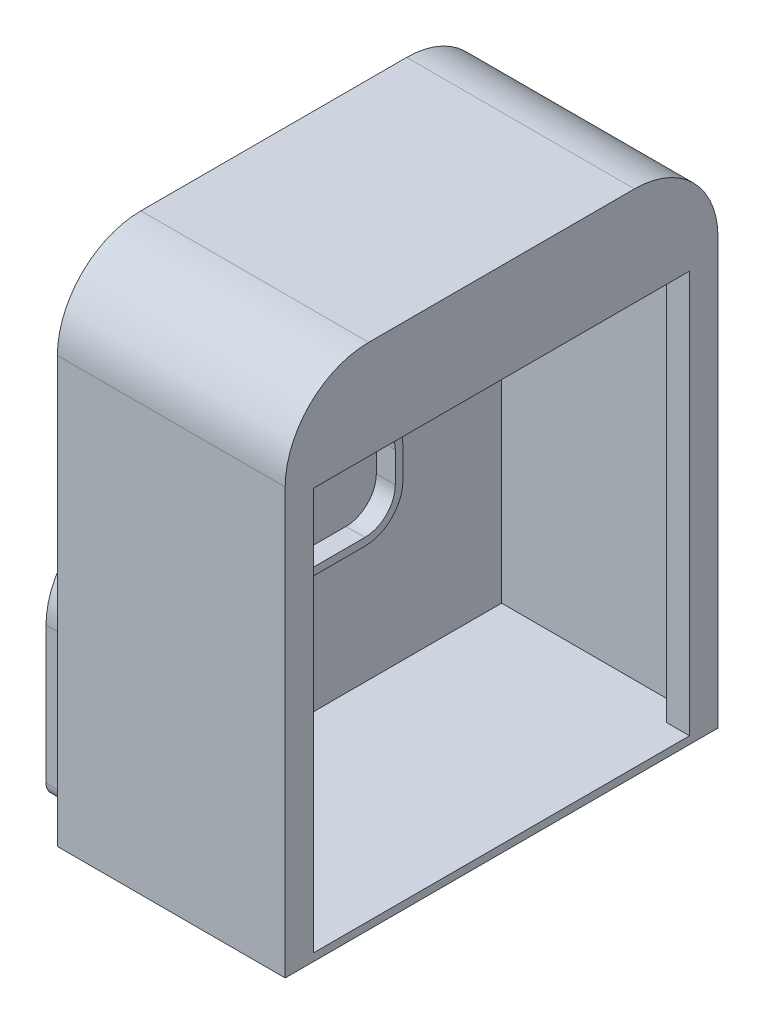
SolidWorks part; units mm, degrees
ref_plane "Front Plane" through (0, 0, 0) normal (0, 0, 1) x (1, 0, 0)
ref_plane "Top Plane" through (0, 0, 0) normal (0, 1, 0) x (1, 0, 0)
ref_plane "Right Plane" through (0, 0, 0) normal (1, 0, 0) x (0, 0, -1)
sketch "Sketch2" plane through (0, 0, 0) normal (1, 0, 0) x (0, 0, -1)
  line L1 (-7, -6) -> (7, -6)
  line L2 (-11, -2) -> (-11, 2)
  line L3 (-7, 6) -> (7, 6)
  line L4 (11, -2) -> (11, 2)
  line L5 (-11, -6) -> (11, 6) construction
  line L6 (-11, 6) -> (11, -6) construction
  arc A0 (-7, -6) -> (-11, -2) centre (-7, -2) cw
  arc A1 (7, 6) -> (11, 2) centre (7, 2) cw
  arc A2 (7, -6) -> (11, -2) centre (7, -2) ccw
  arc A3 (-11, 2) -> (-7, 6) centre (-7, 2) cw
  point P0 (0, 0)
  dimension "D3" = 4
  dimension "D1" = 22
  dimension "D2" = 12
extrude "Extrude-Thin1" add sketch "Sketch2" along normal blind 5 thin thin type one direction wall 1
sketch "Sketch3" plane through (0, 0, 0) normal (1, 0, 0) x (0, 0, -1)
  line L0 (27.5, -25) -> (-27.5, -25)
  line L1 (27.5, -25) -> (27.5, 30)
  line L2 (-27.5, -25) -> (-27.5, 30)
  line L3 (17.5, 40) -> (-17.5, 40)
  arc A0 (27.5, 30) -> (17.5, 40) centre (17.5, 30) ccw
  arc A1 (-27.5, 30) -> (-17.5, 40) centre (-17.5, 30) cw
  dimension "D5" = 10
  dimension "D1" = 25
  dimension "D2" = 40
  dimension "D3" = 27.5
  dimension "D4" = 27.5
extrude "Boss-Extrude1" add sketch "Sketch3" along normal blind 2.5
extrude "Extrude-Thin2" add sketch "Sketch3<2>" along normal blind 30 thin thin type one direction wall 1
sketch "Sketch3<2>" plane through (0, 0, 0) normal (1, 0, 0) x (0, 0, -1) same geometry as "Sketch3"
sketch "Sketch8" plane through (0, 0, 0) normal (-1, 0, 0) x (0, 0, 1)
  line L0 (28.5, -26) -> (-28.5, -26) construction
  line L1 (-23, -25) -> (23, -25)
  line L2 (-25, -23) -> (-25, -5)
  line L3 (-15, 5) -> (15, 5)
  line L4 (25, -23) -> (25, -5)
  line L5 (-25, -25) -> (25, 5) construction
  line L6 (-25, 5) -> (25, -25) construction
  arc A0 (15, 5) -> (25, -5) centre (15, -5) cw
  arc A1 (-25, -5) -> (-15, 5) centre (-15, -5) cw
  arc A2 (23, -25) -> (25, -23) centre (23, -23) ccw
  arc A3 (-23, -25) -> (-25, -23) centre (-23, -23) cw
  point P0 (0, -10)
  dimension "D4" = 10
  dimension "D5" = 2
  dimension "D1" = 50
  dimension "D2" = 1
  dimension "D3" = 10
sketch "Sketch9" plane through (30, 0, 0) normal (1, 0, 0) x (0, 0, -1)
  line L0 (27.5, -25) -> (27.5, 30) construction
  line L1 (-27.5, 30) -> (-27.5, -25) construction
  line L2 (-27.5, -25) -> (27.5, -25) construction
  line L3 (27.5, -25) -> (27.5, 30)
  line L4 (-27.5, 30) -> (-27.5, -25)
  line L5 (-27.5, -25) -> (-24.75, -25)
  line L6 (-24.75, -25) -> (-24.75, 28)
  line L7 (24.75, -25) -> (24.75, 28)
  line L8 (24.75, -25) -> (27.5, -25)
  line L9 (-24.75, 28) -> (24.75, 28)
  line L10 (17.5, 40) -> (-17.5, 40) construction
  line L11 (17.5, 40) -> (-17.5, 40)
  arc A4 (27.5, 30) -> (17.5, 40) centre (17.5, 30) ccw construction
  arc A5 (-17.5, 40) -> (-27.5, 30) centre (-17.5, 30) ccw construction
  arc A6 (27.5, 30) -> (17.5, 40) centre (17.5, 30) ccw
  arc A7 (-17.5, 40) -> (-27.5, 30) centre (-17.5, 30) ccw
  dimension "D1" = 2.75
  dimension "D2" = 2.75
  dimension "D3" = 12
extrude "Boss-Extrude4" add sketch "Sketch9" against normal blind 3
extrude "Boss-Extrude3" add sketch "Sketch8" along normal blind 5
sketch "Sketch11" plane through (0, 0, 0) normal (-1, 0, 0) x (0, 0, 1)
  line L0 (-13.7046, 21.2414) -> (13.6901, 21.2414) construction
  line L1 (-8.0073, 21.2414) -> (-8.0073, 22.2414)
  line L2 (-8.0073, 22.2414) -> (-6.0073, 22.2414)
  line L3 (-6.0073, 21.2414) -> (-8.0073, 21.2414)
  line L4 (5.9927, 22.2414) -> (7.9927, 22.2414)
  line L5 (7.9927, 22.2414) -> (7.9927, 21.2414)
  line L6 (7.9927, 21.2414) -> (5.9927, 21.2414)
  line L7 (5.9927, 21.2414) -> (4.9927, 21.2414)
  line L8 (-5.0073, 21.2414) -> (-6.0073, 21.2414)
  line L9 (-28.5, -26) -> (-28.5, 30) construction
  line L10 (28.5, -26) -> (-28.5, -26) construction
  ellipse E0 centre (-0.0073, 24.5757) end of major axis (2.1355, 24.5757) minor radius 0.9532
  spline S0 degree 2 poles (-6.0073, 22.2414) (-0.0073, 35.2414) (5.9927, 22.2414) knots 0 0 0 1 1 1
  spline S1 degree 2 poles (-5.0073, 21.2414) (-0.0073, 34.2414) (4.9927, 21.2414) knots 0 0 0 1 1 1
  point P0 (0, 25)
  point P5 (-0.0073, 21.2414)
  point P6 (-0.0073, 27.7414)
  point P7 (-6.0073, 21.2414)
  point P10 (-0.0073, 21.2414)
  point P11 (5.9927, 21.2414)
  point P12 (-0.0073, 28.7414)
  point P13 (-6.0073, 22.2414)
  point P14 (5.9927, 22.2414)
  point P17 (-8.0073, 21.2414)
  point P19 (7.9927, 22.2414)
  point P20 (7.9927, 21.2414)
  point P21 (-8.0073, 22.2414)
  point P25 (-5.0073, 21.2414)
  point P28 (4.9927, 21.2414)
  dimension "D1" = 25
wrap "Wrap1" sketch "Sketch11" wrap type scribe source sketch "Sketch11"
